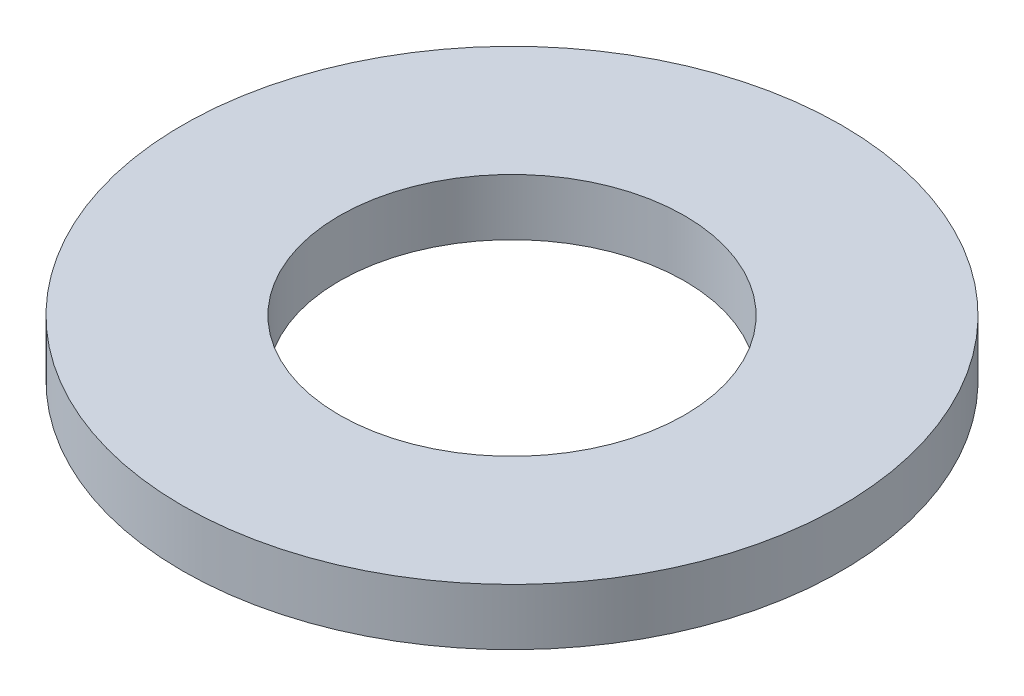
SolidWorks part; units mm, degrees
ref_plane "Front Plane" through (0, 0, 0) normal (0, 0, 1) x (1, 0, 0)
ref_plane "Top Plane" through (0, 0, 0) normal (0, 1, 0) x (1, 0, 0)
ref_plane "Right Plane" through (0, 0, 0) normal (1, 0, 0) x (0, 0, -1)
sketch "Sketch1" plane through (0, 0, 0) normal (0, 1, 0) x (1, 0, 0)
  circle A0 centre (0, 0) radius 52.5
  dimension "FLANGE_OD" = 105
extrude "Boss-Extrude1" add sketch "Sketch1" along normal blind 9
sketch "Sketch2" plane through (0, 0, 0) normal (0, 1, 0) x (1, 0, 0)
  circle A0 centre (0, 0) radius 27.5
  dimension "BORE_D" = 55
extrude "Cut-Extrude1" cut sketch "Sketch2" along normal through all
sketch "Sketch3" plane through (0, 9, 0) normal (0, 1, 0) x (1, 0, 0)
  circle A0 centre (0, 0) radius 20.6935 construction
  circle A1 centre (-20.6935, 0) radius 3.8144
  dimension "BOLT_D" = 7.6287
  dimension "BOLT_PCD" = 41.3871
extrude "Cut-Extrude2" cut sketch "Sketch3" against normal blind 6.1864 rebuild error yes
pattern_circular "CirPattern1" count 6 over 360 rebuild error yes
